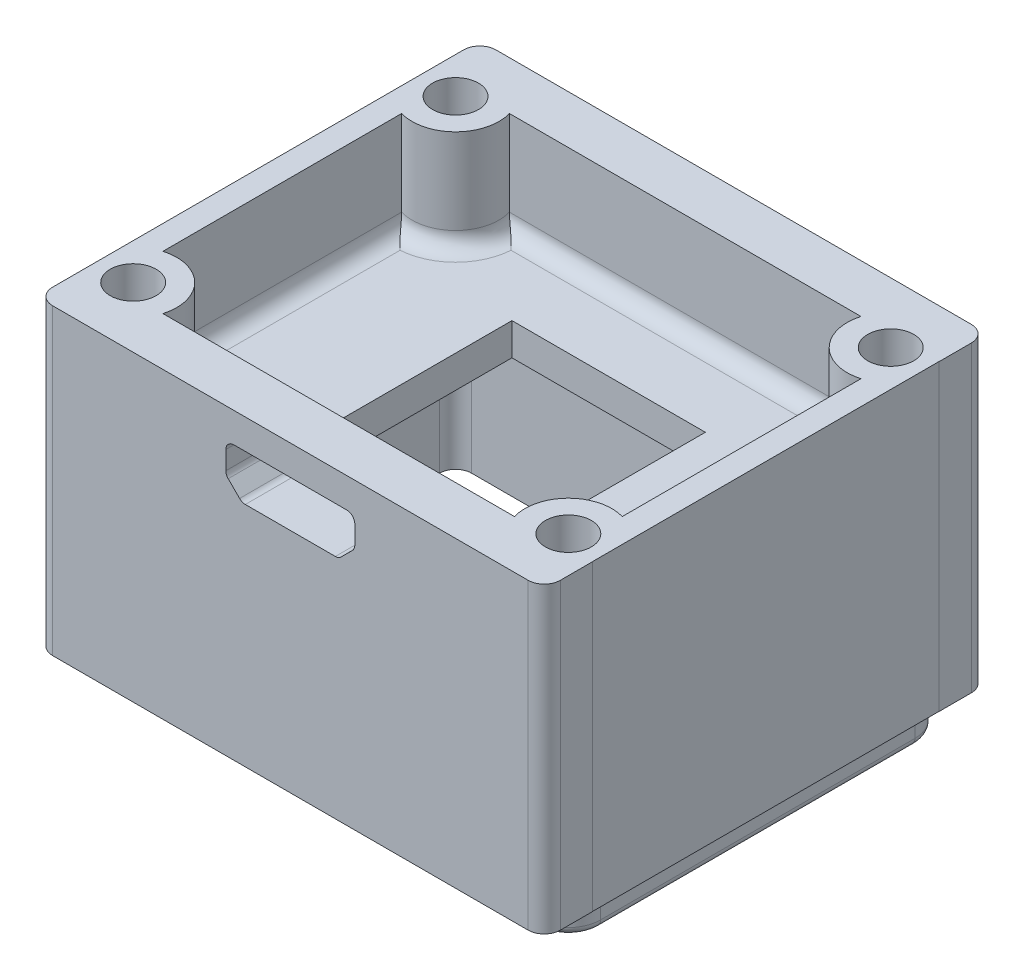
SolidWorks part; units mm, degrees
ref_plane "前视基准面" through (0, 0, 0) normal (0, 0, 1) x (1, 0, 0)
ref_plane "上视基准面" through (0, 0, 0) normal (0, 1, 0) x (1, 0, 0)
ref_plane "右视基准面" through (0, 0, 0) normal (1, 0, 0) x (0, 0, -1)
other "Configuration Table"
ref_plane "基准面1" through (0, 19.5, 0) normal (0, 1, 0) x (1, 0, 0)
sketch "草图1" plane through (0, 19.5, 0) normal (0, 1, 0) x (1, 0, 0)
  line L0 (-15.7466, 13.75) -> (-15.7466, -13.75)
  line L1 (-15.7466, -13.75) -> (15.7538, -13.75)
  line L2 (15.7538, -13.75) -> (15.7538, 13.75)
  line L3 (15.7538, 13.75) -> (-15.7466, 13.75)
extrude "凸台-拉伸1" add sketch "草图1" against normal blind 18.8
sketch "草图2" plane through (0, 0.7, 0) normal (0, -1, 0) x (1, 0, 0)
  line L0 (15.7538, -10.75) -> (15.7538, 10.75)
  line L1 (15.7538, 10.75) -> (15.7466, 10.75)
  line L2 (15.7466, 10.75) -> (15.7466, -10.75)
  line L3 (15.7466, -10.75) -> (15.7538, -10.75)
extrude "切除-拉伸1" cut sketch "草图2" against normal blind 18.8
sketch "草图3" plane through (0, 0.7, 0) normal (0, -1, 0) x (1, 0, 0)
  line L0 (15.25, -11.75) -> (-15.25, -11.75)
  line L1 (-15.25, -11.75) -> (-15.25, 11.75)
  line L2 (-15.25, 11.75) -> (15.25, 11.75)
  line L3 (15.25, 11.75) -> (15.25, -11.75)
extrude "凸台-拉伸2" add sketch "草图3" along normal blind 1.7
sketch "草图4" plane through (0, -1, 0) normal (0, -1, 0) x (1, 0, 0)
  line L0 (-14.25, 10.75) -> (-14.25, -10.75)
  line L1 (-14.25, -10.75) -> (14.25, -10.75)
  line L2 (14.25, -10.75) -> (14.25, 10.75)
  line L3 (14.25, 10.75) -> (-14.25, 10.75)
extrude "切除-拉伸2" cut sketch "草图4" against normal blind 12.2
sketch "草图5" plane through (0, 11.2, 0) normal (0, -1, 0) x (1, 0, 0)
  line L0 (7.9, -7.9) -> (-7.9, -7.9)
  line L1 (-7.9, -7.9) -> (-7.9, 7.9)
  line L2 (-7.9, 7.9) -> (7.9, 7.9)
  line L3 (7.9, 7.9) -> (7.9, -7.9)
extrude "凸台-拉伸3" add sketch "草图5" along normal blind 0.8
sketch "草图6" plane through (0, 19.5, 0) normal (0, 1, 0) x (-1, 0, 0)
  line L0 (-14.25, 7.4063) -> (-14.25, -7.4063)
  line L1 (-10.9063, -10.75) -> (10.9063, -10.75)
  line L2 (14.25, -7.4063) -> (14.25, 7.4063)
  line L3 (10.9063, 10.75) -> (-10.9063, 10.75)
  arc A0 (-10.9063, 10.75) -> (-14.25, 7.4063) centre (-13.5, 10) cw
  arc A1 (-14.25, -7.4063) -> (-10.9063, -10.75) centre (-13.5, -10) cw
  arc A2 (10.9063, -10.75) -> (14.25, -7.4063) centre (13.5, -10) cw
  arc A3 (14.25, 7.4063) -> (10.9063, 10.75) centre (13.5, 10) cw
extrude "切除-拉伸3" cut sketch "草图6" against normal blind 6.3
sketch "草图7" plane through (0, 10.4, 0) normal (0, -1, 0) x (1, 0, 0)
  line L0 (7.1, -7.1) -> (7.1, 7.1)
  line L1 (7.1, 7.1) -> (-7.1, 7.1)
  line L2 (-7.1, 7.1) -> (-7.1, -7.1)
  line L3 (-7.1, -7.1) -> (7.1, -7.1)
extrude "切除-拉伸4" cut sketch "草图7" against normal blind 0.8
sketch "草图8" plane through (0, 13.2, 0) normal (0, 1, 0) x (-1, 0, 0)
  line L0 (-6, -6) -> (6, -6)
  line L1 (6, -6) -> (6, 6)
  line L2 (6, 6) -> (-6, 6)
  line L3 (-6, 6) -> (-6, -6)
extrude "切除-拉伸5" cut sketch "草图8" against normal through all
sketch "草图9" plane through (0, 0, 13.75) normal (0, 0, 1) x (1, 0, 0)
  line L0 (-4, 17.65) -> (-4, 15.8)
  line L1 (-4, 15.8) -> (-3, 14.8)
  line L2 (-3, 14.8) -> (3, 14.8)
  line L3 (3, 14.8) -> (4, 15.8)
  line L4 (4, 15.8) -> (4, 17.65)
  line L5 (4, 17.65) -> (-4, 17.65)
extrude "切除-拉伸6" cut sketch "草图9" against normal up to next
hole_wizard "M2.5 间隙孔1" positions "草图11" profile "草图10" hole size "M2.5" standard "ANSI Metric"
sketch "草图11" plane through (0, 19.5, 0) normal (0, 1, 0) x (1, 0, 0)
  point P0 (13.5, 10)
  point P1 (13.5, -10)
  point P2 (-13.5, -10)
  point P3 (-13.5, 10)
sketch "草图10" plane through (13.5, 19.5, -10) normal (1, 0, 0) x (0, 0, 1)
  line L0 (0, 0) -> (0, 5.5)
  line L1 (0, 5.5) -> (1.425, 5.5)
  line L2 (1.425, 5.5) -> (1.425, 0)
  line L5 (1.425, 0) -> (0, 0)
  line L10 (0, 5.5) -> (-1.425, 5.5) construction
  line L11 (0, -6.35) -> (0, 107.95) construction
  dimension "孔直径" = 2.85
  dimension "孔深度" = 5.5
  dimension "导头角度" = 180
fillet "圆角1" radius 2 4 edges at (-15.25, -0.15, 11.75) (15.25, -0.15, 11.75) (-15.25, -0.15, -11.75) (15.25, -0.15, -11.75) tangent propagation no
fillet "圆角2" radius 0.5 14 edges at (-14.6642, -1, -11.1642) (-15.25, -1, 0) (0, -1, -11.75) (-14.6642, -1, 11.1642) (14.6642, -1, -11.1642) (0, -1, 11.75) (15.25, -1, 0) (14.6642, -1, 11.1642) (3, 14.8, 12.25) (4, 17.65, 12.25) (-4, 15.8, 12.25) (4, 15.8, 12.25) (-3, 14.8, 12.25) (-4, 17.65, 12.25) tangent propagation no
fillet "圆角3" radius 1 16 edges at (14.25, 5.1, 10.75) (-15.7466, 10.1, -13.75) (-14.25, 13.2, 0) (-11.5908, 13.2, -8.0908) (-11.5908, 13.2, 8.0908) (0, 13.2, -10.75) (0, 13.2, 10.75) (11.5908, 13.2, -8.0908) (11.5908, 13.2, 8.0908) (14.25, 13.2, 0) (-14.25, 5.1, -10.75) (15.7538, 10.1, 13.75) (-15.7466, 10.1, 13.75) (15.7538, 10.1, -13.75) (14.25, 5.1, -10.75) (-14.25, 5.1, 10.75) tangent propagation no
sketch "草图12" plane through (0, 14, 0) normal (0, 1, 0) x (-1, 0, 0)
  circle A0 centre (-13.5, -10) radius 1.425
sketch "草图13" plane through (0, 14, 0) normal (0, 1, 0) x (-1, 0, 0)
  circle A0 centre (13.5, -10) radius 1.425
sketch "草图14" plane through (0, 14, 0) normal (0, 1, 0) x (-1, 0, 0)
  circle A0 centre (13.5, 10) radius 1.425
sketch "草图15" plane through (0, 14, 0) normal (0, 1, 0) x (-1, 0, 0)
  circle A0 centre (-13.5, 10) radius 1.425
